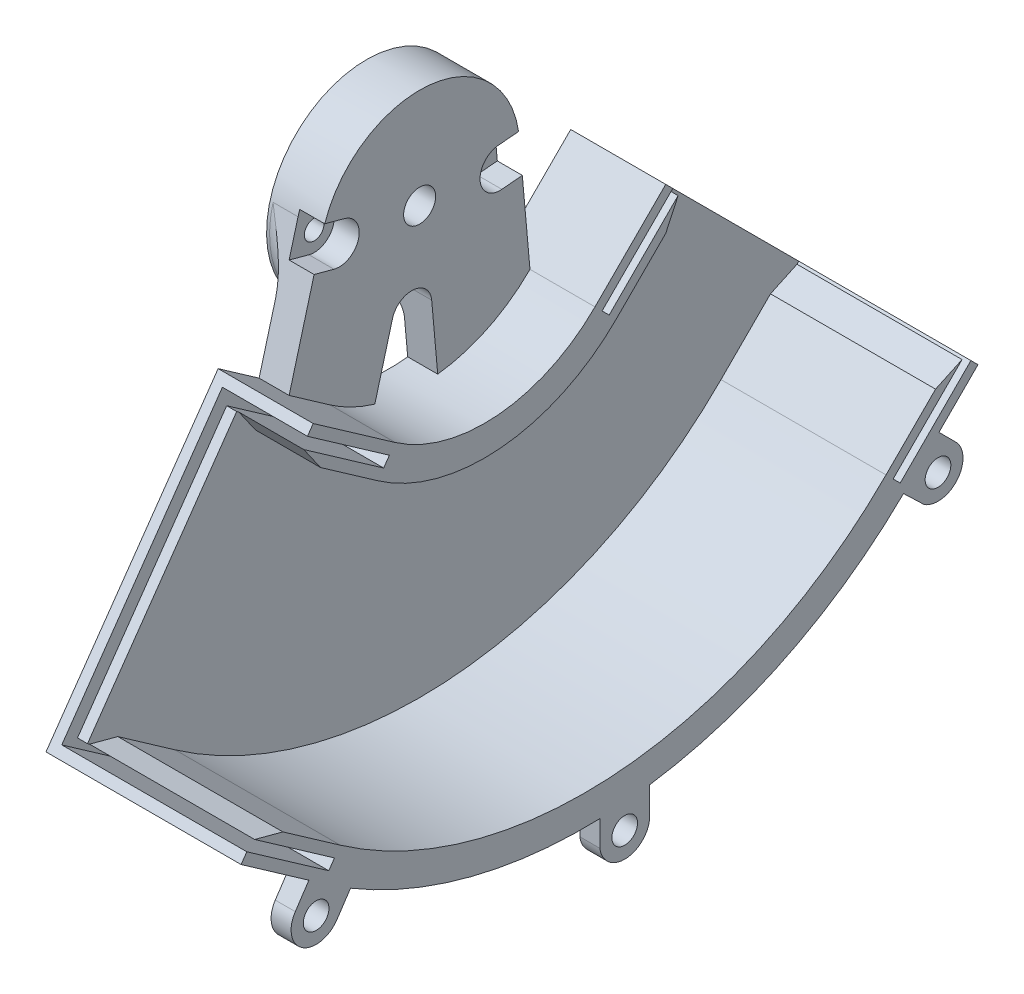
SolidWorks part; units mm, degrees
ref_plane "Front Plane" through (0, 0, 0) normal (0, 0, 1) x (1, 0, 0)
ref_plane "Top Plane" through (0, 0, 0) normal (0, 1, 0) x (1, 0, 0)
ref_plane "Right Plane" through (0, 0, 0) normal (1, 0, 0) x (0, 0, -1)
sketch "Sketch3" plane through (0, 0, 0) normal (1, 0, 0) x (0, 0, -1)
  line L0 (-22.7274, -32.4581) -> (-62.0633, -88.6355)
  line L1 (28.0184, -28.0184) -> (76.5118, -76.5118)
  line L2 (-22.7274, -32.4581) -> (0, 0) construction
  line L3 (0, 0) -> (28.0184, -28.0184) construction
  line L4 (0, 40.513) -> (0, -40.513) construction
  line L5 (-62.0633, -88.6355) -> (-66.4339, -94.8775)
  line L6 (76.5118, -76.5118) -> (81.8999, -81.8999)
  arc A2 (-62.0633, -88.6355) -> (76.5118, -76.5118) centre (0, 0) ccw
  arc A4 (-27.098, -38.7) -> (33.4066, -33.4066) centre (0, 0) ccw
  arc A5 (-22.7274, -32.4581) -> (28.0184, -28.0184) centre (0, 0) ccw
  arc A6 (-66.4339, -94.8775) -> (81.8999, -81.8999) centre (0, 0) ccw
  dimension "D1" = 216.408
  dimension "D2" = 135
  dimension "D3" = 94.488
  dimension "D4" = 7.62
  dimension "D6" = 7.62
  dimension "D5" = 80
extrude "Base extrude" add sketch "Sketch3" along normal blind 58.42 contours L5 A6 L6 A2 | A5 L0 A4 L1 region at (0, -39.9408, -3.4944) region at (0, -109.321, -9.5643)
sketch "Sketch4" plane through (58.42, 0, 0) normal (1, 0, 0) x (0, 0, -1)
  line L0 (-66.4339, -94.8775) -> (-22.7274, -32.4581)
  line L1 (28.0184, -28.0184) -> (81.8999, -81.8999)
  arc A0 (-22.7274, -32.4581) -> (28.0184, -28.0184) centre (0, 0) ccw
  arc A1 (-22.7274, -32.4581) -> (28.0184, -28.0184) centre (0, 0) ccw construction
  arc A2 (-66.4339, -94.8775) -> (81.8999, -81.8999) centre (0, 0) ccw
  arc A3 (-66.4339, -94.8775) -> (81.8999, -81.8999) centre (0, 0) ccw construction
  arc M1 (28.0184, -28.0184) -> (-22.7274, -32.4581) centre (0, 0) cw
  line M2 (-22.7274, -32.4581) -> (-27.098, -38.7)
  arc M3 (-27.098, -38.7) -> (33.4066, -33.4066) centre (0, 0) ccw
  line M4 (33.4066, -33.4066) -> (28.0184, -28.0184)
extrude "Outer wall" add sketch "Sketch4" along normal blind 7.62 contours L0 A2 L1 M3 | M4 M1 M2 M3 region at (58.42, -79.1939, -6.9286) region at (58.42, -39.9408, -3.4944)
ref_plane "Midplane" through (29.21, 0, 0) normal (-1, 0, 0) x (0, 0, 1)
mirror "Mirror1" about plane through (29.21, 0, 0) normal (-1, 0, 0) of "Outer wall"
sketch "Sketch6" plane through (0, 0, 0) normal (0, 0.5736, 0.8192) x (1, 0, 0)
  line L27 (-5.08, -42.164) -> (63.5, -42.164)
  line L28 (-5.08, -42.164) -> (-5.08, -113.284)
  line L29 (-5.08, -113.284) -> (63.5, -113.284)
  line L30 (63.5, -42.164) -> (63.5, -113.284)
  line L31 (-2.54, -44.704) -> (60.96, -44.704)
  line L32 (-2.54, -44.704) -> (-2.54, -110.744)
  line L33 (-2.54, -110.744) -> (60.96, -110.744)
  line L34 (60.96, -44.704) -> (60.96, -110.744)
  line L35 (58.42, -47.244) -> (0, -47.244) construction
  line L36 (0, -108.204) -> (0, -18.7894) construction
  line L37 (58.42, -18.7894) -> (58.42, -108.204) construction
  line L38 (58.42, -108.204) -> (0, -108.204) construction
  line L40 (0, -47.244) -> (58.42, -47.244)
  line L41 (0, -47.244) -> (0, -108.204)
  line L42 (0, -108.204) -> (58.42, -108.204)
  line L43 (58.42, -47.244) -> (58.42, -108.204)
  line L44 (-7.62, -39.624) -> (66.04, -39.624)
  line L45 (-7.62, -39.624) -> (-7.62, -115.824)
  line L46 (-7.62, -115.824) -> (66.04, -115.824)
  line L47 (66.04, -39.624) -> (66.04, -115.824)
  line M21 (-7.62, -39.624) -> (-7.62, -115.824)
  line M22 (-7.62, -115.824) -> (66.04, -115.824)
  line M23 (66.04, -115.824) -> (66.04, -39.624)
  line M24 (66.04, -39.624) -> (-7.62, -39.624)
  line M25 (58.42, -108.204) -> (0, -108.204)
  line M26 (0, -108.204) -> (0, -47.244)
  line M27 (0, -47.244) -> (58.42, -47.244)
  line M28 (58.42, -47.244) -> (58.42, -108.204)
  dimension "D1" = 2.54
  dimension "D2" = 2.54
  dimension "D3" = 2.54
  dimension "D4" = 2.54
  dimension "D5" = 2.54
  dimension "D6" = 2.54
  dimension "D7" = 2.54
  dimension "D8" = 2.54
extrude "Endcap 1" add sketch "Sketch6" along normal blind 25.4 contours L27 L30 L29 L28 M24 M21 M22 M23 | L34 L31 L32 L33 M28 M25 M26 M27 region at (29.21, -37.3698, 26.1667) region at (29.21, -33.3262, 23.3353)
sketch "Sketch7" plane through (0, 0, 0) normal (0, 0.7071, -0.7071) x (1, 0, 0)
  line L0 (-5.08, 113.284) -> (63.5, 113.284)
  line L1 (-5.08, 113.284) -> (-5.08, 42.164)
  line L2 (-5.08, 42.164) -> (63.5, 42.164)
  line L3 (63.5, 113.284) -> (63.5, 42.164)
  line L4 (-2.54, 110.744) -> (60.96, 110.744)
  line L5 (-2.54, 110.744) -> (-2.54, 44.704)
  line L6 (-2.54, 44.704) -> (60.96, 44.704)
  line L7 (60.96, 110.744) -> (60.96, 44.704)
  line L8 (0, 108.204) -> (58.42, 108.204)
  line L9 (0, 108.204) -> (0, 47.244)
  line L10 (0, 47.244) -> (58.42, 47.244)
  line L11 (58.42, 108.204) -> (58.42, 47.244)
  line L12 (-7.62, 115.824) -> (66.04, 115.824)
  line L13 (-7.62, 115.824) -> (-7.62, 39.624)
  line L14 (-7.62, 39.624) -> (66.04, 39.624)
  line L15 (66.04, 115.824) -> (66.04, 39.624)
  line L16 (58.42, 108.204) -> (0, 108.204) construction
  line L17 (58.42, 47.244) -> (58.42, 108.204) construction
  line L18 (66.04, 115.824) -> (-7.62, 115.824) construction
  line L19 (66.04, 39.624) -> (66.04, 115.824) construction
  line L20 (-7.62, 39.624) -> (-7.62, 115.824) construction
  line L21 (66.04, 39.624) -> (-7.62, 39.624) construction
  line M17 (66.04, 115.824) -> (-7.62, 115.824)
  line M18 (-7.62, 115.824) -> (-7.62, 39.624)
  line M19 (-7.62, 39.624) -> (66.04, 39.624)
  line M20 (66.04, 39.624) -> (66.04, 115.824)
  line M21 (0, 47.244) -> (0, 108.204)
  line M22 (0, 108.204) -> (58.42, 108.204)
  line M23 (58.42, 108.204) -> (58.42, 47.244)
  line M24 (58.42, 47.244) -> (0, 47.244)
  dimension "D1" = 2.54
  dimension "D2" = 2.54
  dimension "D3" = 2.54
  dimension "D4" = 2.54
  dimension "D5" = 2.54
  dimension "D6" = 2.54
  dimension "D7" = 2.54
  dimension "D8" = 2.54
extrude "Endcap 2" add sketch "Sketch7" along normal blind 25.4 contours L0 L3 L2 L1 M20 M17 M18 M19 | L7 L4 L5 L6 M24 M21 M22 M23 region at (29.21, -77.66, -77.66) region at (29.21, -81.1505, -81.1505)
chamfer "Internal Chamfer" distance 7.62 angle 20 4 edges at (29.21, -74.0667, 82.8697) (29.21, -24.1312, 47.9045) (29.21, -58.5513, -94.4723) (29.21, -15.446, -51.3671) first distance on face at (29.21, -81.3511, 72.4665) first distance on face at (29.21, -31.4156, 37.5013) first distance on face at (29.21, -67.5315, -85.492) first distance on face at (29.21, -24.4263, -42.3868)
ref_plane "Plane2" through (0, -13.9736, -1.2225) normal (0, -0.9962, -0.0872) x (-1, 0, 0)
sketch "Sketch10" plane through (0, -13.9736, -1.2225) normal (0, -0.9962, -0.0872) x (-1, 0, 0)
  line L0 (-66.04, 93.9078) -> (7.62, 93.9078) construction
  line L1 (-16.51, 95.5358) -> (-41.91, 95.5358)
  line L2 (-16.51, 95.5358) -> (-16.51, -82.1857)
  line L3 (-16.51, -82.1857) -> (-41.91, -82.1857)
  line L4 (-41.91, 95.5358) -> (-41.91, -82.1857)
  point P4 (-29.21, 93.9078)
  point P5 (-29.21, 95.5358)
  dimension "D1" = 25.4
extrude "Flywheel Hole" cut sketch "Sketch10" along normal up to next
sketch "Sketch11" plane through (-7.62, 0, 0) normal (-1, 0, 0) x (0, 0, 1)
  line L0 (-25.2982, 2.2719) -> (-28.0184, -28.0184)
  line L4 (-3.0636, -22.3183) -> (-4.5937, -39.3568)
  line L5 (6.8995, -21.445) -> (11.3704, -37.9575)
  line L6 (-20.4217, -1.79) -> (20.4217, 1.79) construction
  line L7 (24.5172, 6.6383) -> (33.1306, -25.1737)
  line L8 (43.5339, -17.8892) -> (22.7274, -32.4581) construction
  line L10 (1.5525, -17.7121) -> (-2.2178, 25.303) construction
  line L11 (22.7274, -32.4581) -> (43.5339, -17.8892)
  line L12 (22.7274, -32.4581) -> (33.1306, -25.1737)
  arc A1 (-28.0184, -28.0184) -> (22.7274, -32.4581) centre (0, 0) ccw construction
  circle A3 centre (0, 0) radius 4.064
  arc A4 (24.5172, 6.6383) -> (-25.2982, 2.2719) centre (0, 0) ccw
  circle A6 centre (-20.4217, -1.79) radius 2.5
  circle A7 centre (20.4217, 1.79) radius 2.5
  arc A8 (-3.0636, -22.3183) -> (6.8995, -21.445) centre (1.9961, -22.7727) cw
  arc A11 (11.3704, -37.9575) -> (22.7274, -32.4581) centre (0, 0) ccw
  arc A12 (-28.0184, -28.0184) -> (22.7274, -32.4581) centre (0, 0) ccw
  arc A13 (-28.0184, -28.0184) -> (-4.5937, -39.3568) centre (0, 0) ccw
  point P22 (0, 0)
  dimension "D3" = 8.128
  dimension "D2" = 25.4
  dimension "D1" = 5
  dimension "D5" = 5.08
  dimension "D4" = 41
  dimension "D7" = 43.18
  dimension "D6" = 0
extrude "Flywheel holder" add sketch "Sketch11" against normal blind 7.62
sketch "Sketch12" plane through (-7.62, 0, 0) normal (-1, 0, 0) x (0, 0, 1)
  circle A0 centre (0, 0) radius 14.605
  dimension "D1" = 29.21
extrude "Motor insert" cut sketch "Sketch12" against normal blind 6.35
sketch "Sketch13" plane through (66.04, 0, 0) normal (1, 0, 0) x (0, 0, -1)
  line L1 (-110.5367, 4.1813) -> (110.9716, 4.1813)
  line L2 (-110.5367, 4.1813) -> (-110.5367, -123.3274)
  line L3 (-110.5367, -123.3274) -> (110.9716, -123.3274)
  line L4 (110.9716, 4.1813) -> (110.9716, -123.3274)
extrude "Cut-Extrude1" cut sketch "Sketch13" against normal up to surface (24.13 mm away) up to face at (41.91, -26.9401, -2.3569)
sketch "Sketch14" plane through (41.91, 0, 0) normal (1, 0, 0) x (0, 0, -1)
  line L0 (-73.4762, -97.5482) -> (-70.0245, -92.3633)
  line L1 (-66.4339, -94.8775) -> (-87.2404, -80.3086) construction
  line L2 (-70.0245, -92.3633) -> (-59.4528, -99.401)
  line L3 (-59.4528, -99.401) -> (-62.9045, -104.586)
  line L4 (3.8593, -122.286) -> (3.8593, -115.7597)
  line L5 (3.8593, -115.7597) -> (16.51, -114.6413)
  line L6 (16.51, -114.6413) -> (16.51, -121.4959)
  line L7 (86.1731, -87.8533) -> (80.953, -82.836)
  line L8 (80.953, -82.836) -> (89.843, -73.7664)
  line L10 (89.843, -73.7664) -> (94.5478, -78.4712)
  line L11 (99.8604, -63.9394) -> (81.8999, -81.8999) construction
  circle A0 centre (-68.1904, -101.0671) radius 3.2639
  circle A1 centre (89.7004, -82.5731) radius 3.2639
  circle A2 centre (10.16, -121.4959) radius 3.2639
  arc A3 (-73.4762, -97.5482) -> (-62.9045, -104.586) centre (-68.1904, -101.0671) ccw
  arc A4 (3.8593, -122.286) -> (16.51, -121.4959) centre (10.16, -121.4959) ccw
  arc A5 (86.1731, -87.8533) -> (93.8023, -77.7257) centre (89.7004, -82.5731) ccw
  arc A6 (-66.4339, -94.8775) -> (81.8999, -81.8999) centre (0, 0) ccw construction
  line M9 (-87.2404, -80.3086) -> (-66.4339, -94.8775)
  arc M10 (-66.4339, -94.8775) -> (81.8999, -81.8999) centre (0, 0) ccw
  line M11 (81.8999, -81.8999) -> (99.8604, -63.9394)
  dimension "D7" = 6.5278
  dimension "D8" = 12.7
  dimension "D1" = 121.92
  dimension "D2" = 121.92
  dimension "D3" = 19.05
  dimension "D4" = 10.16
  dimension "D5" = 121.92
  dimension "D6" = 10.16
  dimension "D9" = 12.7
  dimension "D10" = 12.7
  dimension "D11" = 12.7
extrude "Joining connectors" add sketch "Sketch14" against normal blind 5.08 contours L7 A5 L10 A1 M11 M10 | L0 A3 L3 A0 M10 M9 | L5 L6 A4 L4 | A2 region at (41.91, -82.521, -81.5777) region at (41.91, -95.0739, 71.573)
sketch "Sketch15" plane through (-7.62, 0, 0) normal (-1, 0, 0) x (0, 0, 1)
  line L0 (-35.56, -110.2301) -> (-35.56, -132.08)
  line L1 (-35.56, -132.08) -> (30.48, -132.08)
  line L2 (30.48, -132.08) -> (30.48, -111.7415)
  circle A0 centre (20.32, -121.92) radius 3.2639
  circle A1 centre (-25.4, -121.92) radius 3.2639
  arc A2 (-81.8999, -81.8999) -> (66.4339, -94.8775) centre (0, 0) ccw construction
  circle A4 centre (-10.16, -121.4959) radius 3.2639
  arc A5 (-81.8999, -81.8999) -> (66.4339, -94.8775) centre (0, 0) ccw
  arc A6 (-81.8999, -81.8999) -> (66.4339, -94.8775) centre (0, 0) ccw
  circle A7 centre (-10.16, -121.4959) radius 3.2639 construction
  arc M16 (-81.8999, -81.8999) -> (66.4339, -94.8775) centre (0, 0) ccw
  dimension "D1" = 6.5278
  dimension "D2" = 25.4
  dimension "D3" = 20.32
  dimension "D5" = 10.16
  dimension "D6" = 10.16
  dimension "D7" = 10.16
  dimension "D8" = 121.92
  dimension "D4" = 0
extrude "80-20 connectors" add sketch "Sketch15" against normal blind 5.08 contours L1 L2 L0 A4 A1 A0 M16 region at (-7.62, -123.2019, -2.8038)
fillet "Fillet1" radius 30.48 2 edges at (-5.08, -111.7415, 30.48) (-5.08, -110.2301, -35.56)
fillet "Fillet2" radius 15.24 2 edges at (-5.08, -132.08, -35.56) (-5.08, -132.08, 30.48)
sketch "Sketch18" plane through (-1.27, 0, 0) normal (-1, 0, 0) x (0, 0, 1)
  circle A0 centre (0, 0) radius 4.064
  circle A1 centre (0, 0) radius 14.605
  circle A2 centre (0, 0) radius 14.605 construction
  circle A3 centre (0, 0) radius 4.064 construction
extrude "Boss-Extrude3" add sketch "Sketch18" along normal blind 5.842
sketch "Sketch20" plane through (-7.62, 0, 0) normal (-1, 0, 0) x (0, 0, 1)
  line L5 (6.8995, -21.445) -> (11.3704, -37.9575)
  line L6 (-4.5937, -39.3568) -> (-3.0636, -22.3183)
  line L7 (6.8995, -21.445) -> (7.6509, -24.2203)
  line L8 (-3.3207, -25.182) -> (-3.0636, -22.3183)
  circle A0 centre (0, 0) radius 14.605
  arc A1 (7.6509, -24.2203) -> (-3.3207, -25.182) centre (0, 0) ccw
  circle A2 centre (20.4217, 1.79) radius 2.5
  circle A3 centre (-20.4217, -1.79) radius 2.5
  circle A4 centre (-20.4217, -1.79) radius 2.5 construction
  circle A5 centre (20.4217, 1.79) radius 2.5 construction
  arc A6 (24.5172, 6.6383) -> (-25.2982, 2.2719) centre (0, 0) ccw construction
  circle A7 centre (0, 0) radius 14.605 construction
  arc A12 (6.8995, -21.445) -> (-3.0636, -22.3183) centre (1.9961, -22.7727) ccw
  arc A13 (6.8995, -21.445) -> (-3.0636, -22.3183) centre (1.9961, -22.7727) ccw
  dimension "D1" = 0
extrude "Boss-Extrude5" add sketch "Sketch20" along normal blind 5.842
sketch "Sketch21" plane through (0, 0, 0) normal (1, 0, 0) x (0, 0, -1)
  line L0 (-21.7494, -3.1134) -> (-32.7185, -0.1434)
  line L2 (-32.7185, -0.1434) -> (-30.0632, 9.6635)
  line L3 (-30.0632, 9.6635) -> (-19.094, 6.6934)
  line L4 (-33.1306, -25.1737) -> (-24.5172, 6.6383) construction
  line L5 (20.8761, -6.8496) -> (31.3766, -5.9066)
  line L6 (31.3766, -5.9066) -> (30.4678, 4.2126)
  line L7 (30.4678, 4.2126) -> (19.9673, 3.2696)
  line L8 (25.2982, 2.2719) -> (28.0184, -28.0184) construction
  arc A0 (-21.7494, -3.1134) -> (-19.094, 6.6934) centre (-20.4217, 1.79) ccw
  arc A1 (19.9673, 3.2696) -> (20.8761, -6.8496) centre (20.4217, -1.79) ccw
  dimension "D1" = 5.08
  dimension "D2" = 10.16
extrude "Cut-Extrude2" cut sketch "Sketch21" against normal blind 6.35
fillet "Fillet3" radius 5.08 2 edges at (-7.62, -12.1819, 22.2881) (-7.62, -15.8736, -19.829)
